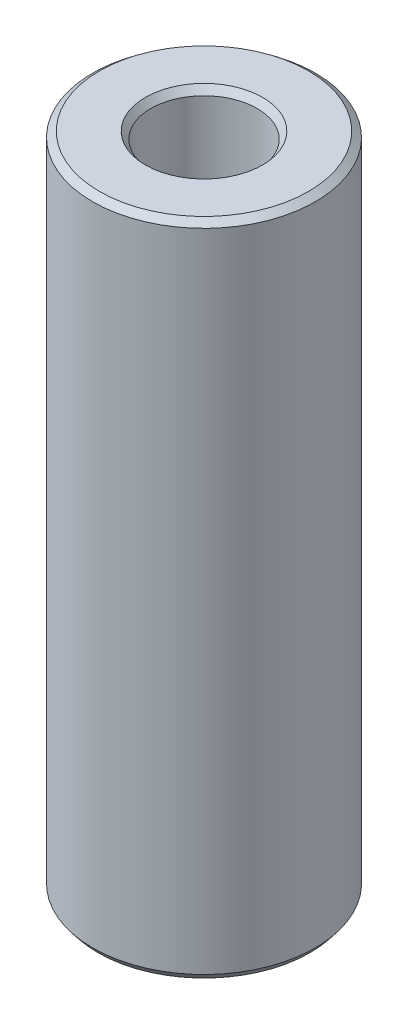
SolidWorks part; units mm, degrees
ref_plane "Front Plane" through (0, 0, 0) normal (0, 0, 1) x (1, 0, 0)
ref_plane "Top Plane" through (0, 0, 0) normal (0, 1, 0) x (1, 0, 0)
ref_plane "Right Plane" through (0, 0, 0) normal (1, 0, 0) x (0, 0, -1)
sketch "Sketch1" plane through (0, 0, 0) normal (0, 1, 0) x (1, 0, 0)
  circle A0 centre (0, 0) radius 57.5
  dimension "SLEEVE_OD" = 115
extrude "Boss-Extrude1" add sketch "Sketch1" along normal blind 339.9179
sketch "Sketch2" plane through (0, 0, 0) normal (0, 1, 0) x (1, 0, 0)
  circle A0 centre (0, 0) radius 27.4607
  dimension "BORE_D" = 54.9214
extrude "Cut-Extrude1" cut sketch "Sketch2" along normal through all
chamfer "Chamfer1" distance 2.7864 angle 52.062 4 edges at (0, 339.9179, 27.4607) (0, 0, 27.4607) (0, 0, 57.5) (0, 339.9179, 57.5) first distance on face at (0, 339.9179, 27.4607) first distance on face at (0, 0, 27.4607) first distance on face at (0, 339.9179, 57.5)
